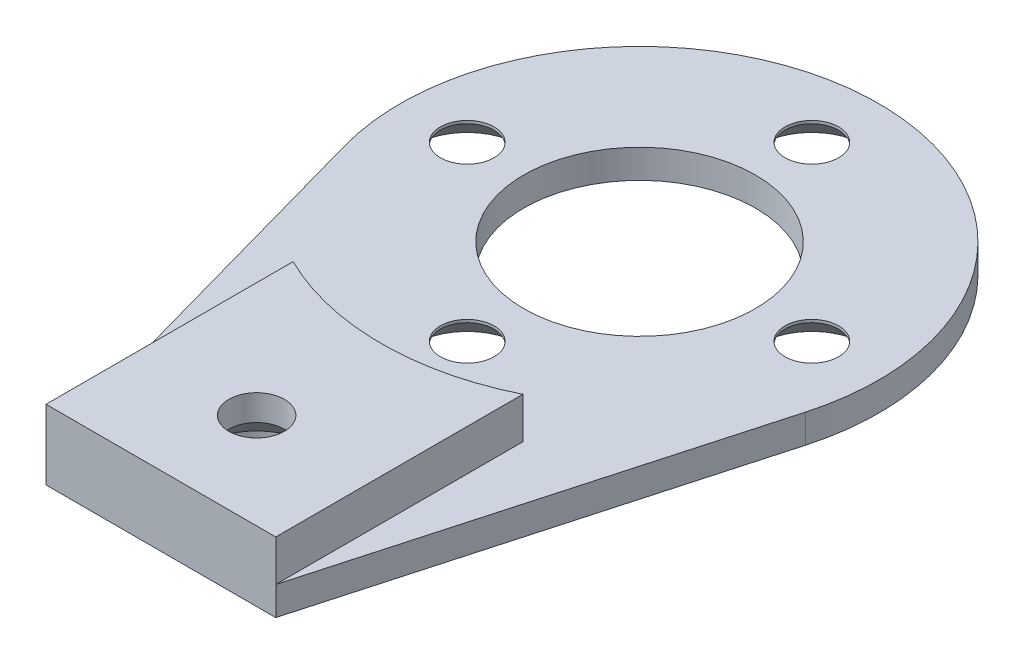
SolidWorks part; units mm, degrees
ref_plane "Front Plane" through (0, 0, 0) normal (0, 0, 1) x (1, 0, 0)
ref_plane "Top Plane" through (0, 0, 0) normal (0, 1, 0) x (1, 0, 0)
ref_plane "Right Plane" through (0, 0, 0) normal (1, 0, 0) x (0, 0, -1)
sketch "Sketch1" plane through (0, 0, 0) normal (0, 1, 0) x (1, 0, 0)
  line L0 (-12.0398, -3.3604) -> (-6, -25)
  line L1 (-6, -25) -> (6, -25)
  line L2 (6, -25) -> (12.0398, -3.3604)
  arc A0 (12.0398, -3.3604) -> (-12.0398, -3.3604) centre (0, 0) ccw
  dimension "D1" = 25
  dimension "D2" = 25
  dimension "D3" = 12
extrude "Boss-Extrude1" add sketch "Sketch1" along normal blind 1.5
sketch "Sketch2" plane through (0, 1.5, 0) normal (0, 1, 0) x (1, 0, 0)
  line L0 (6, -25) -> (12.0398, -3.3604) construction
  line L1 (-6, -25) -> (6, -25) construction
  line L2 (-12.0398, -3.3604) -> (-6, -25) construction
  line L3 (6, -25) -> (12.0398, -3.3604) construction
  line L4 (-6, -25) -> (6, -25) construction
  line L5 (-12.0398, -3.3604) -> (-6, -25) construction
  line L6 (-6, -25) -> (-6, -12.0934)
  line L7 (6, -25) -> (6, -12.0934)
  line L8 (-6, -25) -> (6, -25)
  circle A0 centre (0, 0) radius 13.5 construction
  arc A1 (-6, -12.0934) -> (6, -12.0934) centre (0, 0) ccw
  dimension "D1" = 27
extrude "Boss-Extrude2" add sketch "Sketch2" along normal blind 2.15
sketch "Sketch3" plane through (0, 0, 0) normal (0, -1, 0) x (1, 0, 0)
  circle A0 centre (0, 0) radius 9 construction
  circle A1 centre (0, 9) radius 1.25
  circle A2 centre (9, 0) radius 1.25
  circle A3 centre (0, -9) radius 1.25
  circle A4 centre (-9, 0) radius 1.25
  point P14 (0, 0)
  dimension "D1" = 18
  dimension "D2" = 2.5
  dimension "D3" = 4
hole_wizard "CSK for M2.5 Flat Head Machine Screw1" positions "Sketch4" profile "Sketch5" countersink size "M2.5" standard "ANSI Metric" end condition through all
sketch "Sketch4" plane through (0, 0, 0) normal (0, -1, 0) x (-1, 0, 0)
  point P0 (0, -9)
  point P3 (9, 0)
  point P6 (0, 9)
  point P9 (-9, 0)
sketch "Sketch5" plane through (0, 0, 9) normal (1, 0, 0) x (0, 0, -1)
  line L0 (0, 0) -> (0, 3.65)
  line L1 (0, 3.65) -> (1.4, 3.65)
  line L2 (1.4, 3.65) -> (1.4, 1.35)
  line L3 (1.4, 1.35) -> (2.75, 0)
  line L5 (2.75, 0) -> (0, 0)
  line L6 (-1.4, 1.35) -> (-2.75, 0) construction
  line L11 (0, -6.35) -> (0, 107.95) construction
  dimension "Thru Hole Dia." = 2.8
  dimension "Thru Hole Depth" = 3.65
  dimension "Near C'Sink Dia." = 5.5
  dimension "Near C'Sink Angle" = 90
sketch "Sketch6" plane through (0, 0, 0) normal (0, -1, 0) x (1, 0, 0)
  circle A0 centre (0, 0) radius 6.05
  dimension "D1" = 12.1
extrude "Cut-Extrude1" cut sketch "Sketch6" against normal through all
sketch "Sketch7" plane through (0, 0, 0) normal (0, -1, 0) x (-1, 0, 0)
  line L0 (0, 0) -> (0, -25) construction
  line L1 (6, -25) -> (-6, -25) construction
  circle A0 centre (0, -20) radius 2.75
  circle A1 centre (0, 0) radius 6.05 construction
  point P7 (0, 0)
  dimension "D2" = 5.5
  dimension "D1" = 5
extrude "Cut-Extrude2" cut sketch "Sketch7" against normal blind 1
hole_wizard "CSK for M2.5 Flat Head Machine Screw2" positions "Sketch8" profile "Sketch9" countersink size "M2.5" standard "ANSI Metric"
sketch "Sketch8" plane through (0, 1, 0) normal (0, -1, 0) x (-1, 0, 0)
  point P0 (0, -20)
sketch "Sketch9" plane through (0, 1, 20) normal (1, 0, 0) x (0, 0, -1)
  line L0 (0, 0) -> (0, 8.8712)
  line L1 (0, 8.8712) -> (1.45, 8)
  line L2 (1.45, 8) -> (1.45, 1.3)
  line L3 (1.45, 1.3) -> (2.75, 0)
  line L5 (2.75, 0) -> (0, 0)
  line L6 (-1.45, 1.3) -> (-2.75, 0) construction
  line L10 (0, 8.8712) -> (-1.45, 8) construction
  line L11 (0, -6.35) -> (0, 107.95) construction
  dimension "Hole Dia." = 2.9
  dimension "Hole Depth" = 8
  dimension "Near C'Sink Dia." = 5.5
  dimension "Near C'Sink Angle" = 90
  dimension "Drill Angle" = 118
